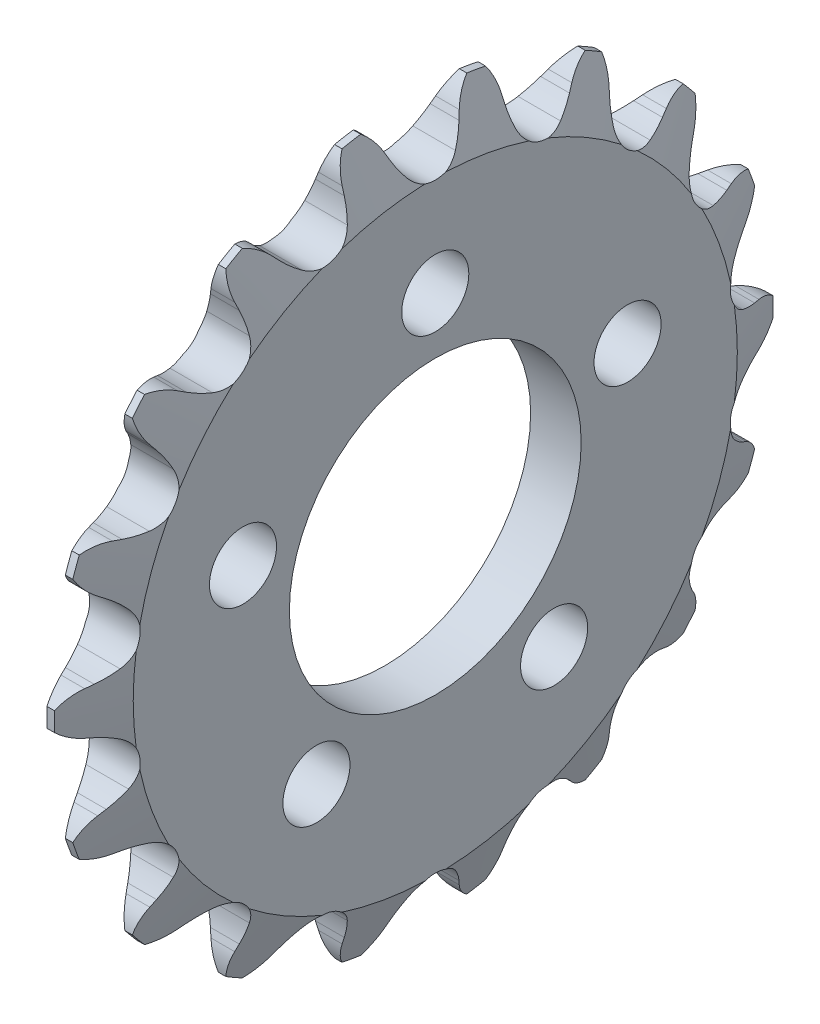
SolidWorks part; units mm, degrees
material "Alloy Steel"
ref_plane "Front Plane" through (0, 0, 0) normal (0, 0, 1) x (1, 0, 0)
ref_plane "Top Plane" through (0, 0, 0) normal (0, 1, 0) x (1, 0, 0)
ref_plane "Right Plane" through (0, 0, 0) normal (1, 0, 0) x (0, 0, -1)
ref_axis "X AXIS" through (-88.99, 0, 0) along (1, 0, 0)
ref_axis "Y AXIS" through (0, -55, 0) along (0, 1, 0)
ref_axis "Z AXIS" through (0, 0, 55) along (0, 0, -1)
other "Freeze***"
sketch "Sketch1" plane through (0, 0, 0) normal (1, 0, 0) x (0, 0, -1)
  line L0 (0, 18.2841) -> (-6.2535, 17.1814) construction
  line L1 (-1.9086, 18.1962) -> (-2.0662, 18.5596)
  line L2 (-1.9086, 18.1962) -> (2.0721, 19.9225) construction
  line L3 (2.0721, 19.9225) -> (0, 18.2841) construction
  line L4 (0, 18.2841) -> (-1.9468, 18.2841) construction
  line L5 (-3.5246, 19.9889) -> (-3.1268, 17.7328) construction
  line L6 (0, 18.2841) -> (0, 16.5867) construction
  circle A0 centre (0, 0) radius 18.2841 construction
  arc A1 (-1.3314, 17.2313) -> (0, 16.5867) centre (0, 18.2841) ccw
  arc A2 (-1.3314, 17.2313) -> (-1.9086, 18.1962) centre (2.0721, 19.9225) cw
  arc A3 (-2.0662, 18.5596) -> (-3.5246, 19.9889) centre (-4.5526, 17.4814) ccw
sketch "Sketch2" plane through (0, 0, 0) normal (0, 0, 1) x (1, 0, 0)
  line L0 (0, 0) -> (0, 19.8716) construction
  line L1 (-0.2064, 19.8716) -> (0.2064, 19.8716)
  line L2 (0.2064, 19.8716) -> (1.397, 16.6966)
  line L3 (1.397, 16.6966) -> (1.397, 0)
  line L4 (-1.397, 0) -> (1.397, 0)
  line L5 (-1.397, 16.6966) -> (-1.397, 0)
  line L6 (-0.2064, 19.8716) -> (-1.397, 16.6966)
  dimension "D1" = 19.8716
  dimension "D2" = 2.794
revolve "Revolve1" add sketch "Sketch2" angle 360 about L4
sketch "Sketch3" plane through (0, 0, 0) normal (1, 0, 0) x (0, 0, -1)
  line L0 (-1.9086, 18.1962) -> (-2.0662, 18.5596) construction
  line L1 (-1.9086, 18.1962) -> (-2.0662, 18.5596)
  line L2 (0, 16.5867) -> (0, 0) construction
  line L3 (1.9086, 18.1962) -> (2.0662, 18.5596)
  arc A0 (-2.0662, 18.5596) -> (-3.5246, 19.9889) centre (-4.5526, 17.4814) ccw construction
  arc A1 (-1.9086, 18.1962) -> (-1.3314, 17.2313) centre (2.0721, 19.9225) ccw construction
  arc A2 (-1.3314, 17.2313) -> (0, 16.5867) centre (0, 18.2841) ccw construction
  arc A3 (-2.0662, 18.5596) -> (-3.5246, 19.9889) centre (-4.5526, 17.4814) ccw
  arc A4 (-1.9086, 18.1962) -> (-1.3314, 17.2313) centre (2.0721, 19.9225) ccw
  arc A5 (-1.3314, 17.2313) -> (1.3314, 17.2313) centre (0, 18.2841) ccw
  arc A6 (1.9086, 18.1962) -> (1.3314, 17.2313) centre (-2.0721, 19.9225) cw
  arc A7 (2.0662, 18.5596) -> (3.5246, 19.9889) centre (4.5526, 17.4814) cw
  arc A8 (-3.5246, 19.9889) -> (3.5246, 19.9889) centre (0, 0) cw
extrude "Cut-Extrude1" cut sketch "Sketch3" against normal through all both and the other way through all contours A8 A3 L1 A4 A5 A6 L3 A7 region at (0, 18.7821, 0)
pattern_circular "CirPattern1" count 18 over 360 about axis through (-88.99, 0, 0) along (1, 0, 0) of "Cut-Extrude1"
sketch "Sketch4" plane through (1.397, 0, 0) normal (1, 0, 0) x (0, 0, -1)
  line L0 (0, 0) -> (0, 11.176) construction
  circle A0 centre (0, 0) radius 8.0645
  circle A1 centre (0, 11.176) radius 1.8542
  circle A2 centre (10.629, 3.4536) radius 1.8542
  circle A3 centre (6.5691, -9.0416) radius 1.8542
  circle A4 centre (-6.5691, -9.0416) radius 1.8542
  circle A5 centre (-10.629, 3.4536) radius 1.8542
  point P15 (0, 0)
  dimension "D1" = 16.129
  dimension "D2" = 5
  dimension "D3" = 3.7084
  dimension "D4" = 11.176
extrude "Cut-Extrude2" cut sketch "Sketch4" against normal through all
equation "\"p\"= 2 / 8"
equation "\"n\"= 18"
equation "\"Dr\"= 0.13"
equation "\"Ds\"= 1.005 * \"Dr\" + 0.003"
equation "\"PD\"= \"p\" * cosec ( 180 / \"n\" )"
equation "\"A\"= 35 + 60 / \"n\""
equation "\"B\"= 18 - 56 / \"n\""
equation "\"ac\"= 0.8 * \"Dr\""
equation "\"ab\"= 1.4 * \"Dr\""
equation "\"D1@Sketch1\"=\"PD\""
equation "\"D2@Sketch1\"=\"p\""
equation "\"D3@Sketch1\"=\"Ds\""
equation "\"D4@Sketch1\"=\"A\""
equation "\"D5@Sketch1\"=\"B\""
equation "\"D6@Sketch1\"=\"ac\""
equation "\"D7@Sketch1\"=\"ab\""
equation "\"D1@Sketch2\"=(\"PD\"+\"p\"/2)/2"
equation "\"D4@Sketch2\"=\"p\"/2"
equation "\"D1@CirPattern1\"=\"n\""
